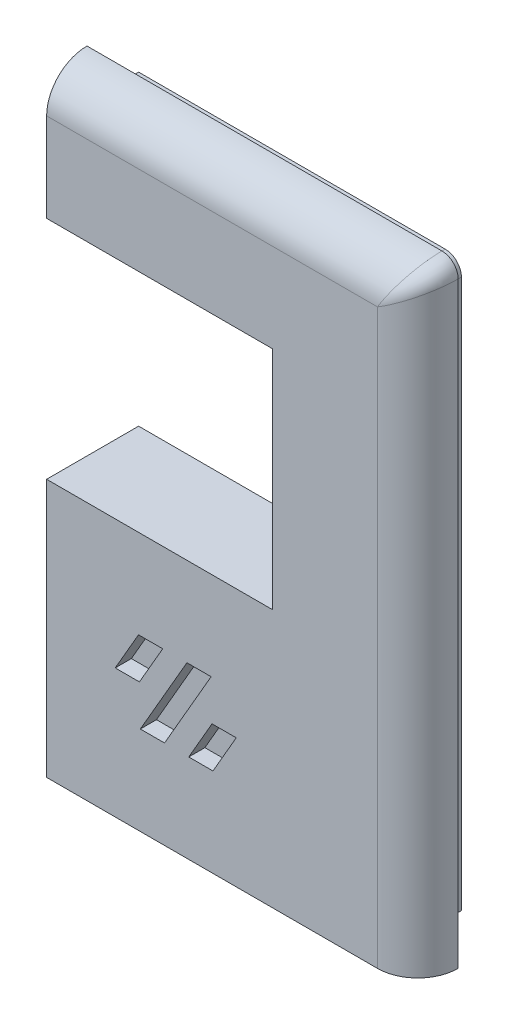
SolidWorks part; units mm, degrees
ref_plane "Front Plane" through (0, 0, 0) normal (0, 0, 1) x (1, 0, 0)
ref_plane "Top Plane" through (0, 0, 0) normal (0, 1, 0) x (1, 0, 0)
ref_plane "Right Plane" through (0, 0, 0) normal (1, 0, 0) x (0, 0, -1)
sketch "Sketch1" plane through (0, 0, 0) normal (0, 0, 1) x (1, 0, 0)
  line L1 (-14.899, 13.3838) -> (5.101, 13.3838)
  line L2 (-14.899, 13.3838) -> (-14.899, -21.6162)
  line L3 (-14.899, -21.6162) -> (5.101, -21.6162)
  line L4 (5.101, 13.3838) -> (5.101, -21.6162)
  dimension "D1" = 20
  dimension "D2" = 35
extrude "Boss-Extrude1" add sketch "Sketch1" along normal blind 3.2
fillet "Fillet1" radius 1 1 edges at (5.101, 13.3838, 1.6)
sketch "Sketch2" plane through (0, 0, 3.2) normal (0, 0, 1) x (1, 0, 0)
  line L0 (-14.899, 13.3838) -> (-14.899, -21.6162) construction
  line L1 (-14.899, -5.6162) -> (-0.899, -5.6162)
  line L2 (-14.899, -5.6162) -> (-14.899, 8.3838)
  line L3 (-14.899, 8.3838) -> (-0.899, 8.3838)
  line L4 (-0.899, -5.6162) -> (-0.899, 8.3838)
  line L5 (-14.899, -21.6162) -> (5.101, -21.6162) construction
  dimension "D1" = 16
  dimension "D2" = 14
  dimension "D3" = 14
extrude "Cut-Extrude1" cut sketch "Sketch2" against normal through all and the other way blind 12.5
sketch "Sketch4" plane through (0, 0, 3.2) normal (0, 0, 1) x (1, 0, 0)
  line L0 (4.101, 13.3838) -> (-14.899, 13.3838) construction
  line L1 (-14.899, 16.3838) -> (8.101, 16.3838)
  line L2 (-14.899, 16.3838) -> (-14.899, -21.6162)
  line L3 (-14.899, -21.6162) -> (8.101, -21.6162)
  line L4 (8.101, 16.3838) -> (8.101, -21.6162)
  line L5 (5.101, -21.6162) -> (5.101, 12.3838) construction
  dimension "D1" = 3
  dimension "D2" = 3
  dimension "D3" = 38
extrude "Boss-Extrude2" add sketch "Sketch4" along normal blind 2.5
fillet "Fillet2" radius 1 1 edges at (8.101, 16.3838, 4.45)
sketch "Sketch5" plane through (0, 0, 3.2) normal (0, 0, -1) x (-1, 0, 0)
  line L1 (0.899, 8.3838) -> (14.899, 8.3838)
  line L2 (0.899, 8.3838) -> (0.899, -5.6162)
  line L3 (0.899, -5.6162) -> (14.899, -5.6162)
  line L4 (14.899, 8.3838) -> (14.899, -5.6162)
extrude "Cut-Extrude2" cut sketch "Sketch5" against normal blind 2.5
fillet "Fillet3" radius 2.5 3 edges at (8.101, -3.1162, 5.7) (7.8081, 16.0909, 5.7) (-3.899, 16.3838, 5.7)
sketch "Sketch6" plane through (0, 0, 0) normal (0, 0, -1) x (-1, 0, 0)
  line L0 (14.899, -21.6162) -> (-5.101, -21.6162) construction
  line L1 (0.899, -5.6162) -> (0.899, 8.3838) construction
  circle A0 centre (-2.101, 5.3838) radius 1.4
  dimension "D1" = 2.8
  dimension "D2" = 27
  dimension "D3" = 3
sketch "Sketch7" plane through (0, 0, 0) normal (0, 0, -1) x (-1, 0, 0)
  line L0 (14.899, -5.6162) -> (14.899, -21.6162) construction
  line L1 (14.899, -21.6162) -> (-5.101, -21.6162) construction
  circle A0 centre (2.899, -13.6162) radius 3.065
  dimension "D1" = 6.13
  dimension "D2" = 12
  dimension "D3" = 8
extrude "Cut-Extrude4" cut sketch "Sketch7" against normal blind 3.1
sketch "Sketch12" plane through (0, 0, 5.7) normal (0, 0, 1) x (1, 0, 0)
  line L0 (-9.2056, -11.1162) -> (-7.7056, -11.1162)
  line L1 (-7.7056, -11.1162) -> (-9.149, -13.6162)
  line L2 (-9.149, -13.6162) -> (-10.649, -13.6162)
  line L3 (-10.649, -13.6162) -> (-9.2056, -11.1162)
  line L4 (-6.2056, -11.1162) -> (-4.7056, -11.1162)
  line L5 (-4.7056, -11.1162) -> (-7.5924, -16.1162)
  line L6 (-7.5924, -16.1162) -> (-9.0924, -16.1162)
  line L7 (-9.0924, -16.1162) -> (-6.2056, -11.1162)
  line L8 (-6.0924, -16.1162) -> (-4.5924, -16.1162)
  line L9 (-4.5924, -16.1162) -> (-3.149, -13.6162)
  line L10 (-3.149, -13.6162) -> (-4.649, -13.6162)
  line L11 (-4.649, -13.6162) -> (-6.0924, -16.1162)
  line L13 (-0.899, -5.6162) -> (-14.899, -5.6162) construction
  line L14 (-14.899, -5.6162) -> (-14.899, -21.6162) construction
  dimension "D1" = 1.5
  dimension "D2" = 1.5
  dimension "D3" = 1.5
  dimension "D4" = 1.5
  dimension "D5" = 1.5
  dimension "D6" = 1.5
  dimension "D7" = 5
  dimension "D10" = 1.5
  dimension "D11" = 1.5
  dimension "D12" = 8
  dimension "D13" = 4.25
extrude "Cut-Extrude5" cut sketch "Sketch12" against normal blind 1
extrude "Boss-Extrude3" add sketch "Sketch6" along normal blind 1.75
fillet "Fillet5" radius 1 1 edges at (0.701, 5.3838, -1.75)
